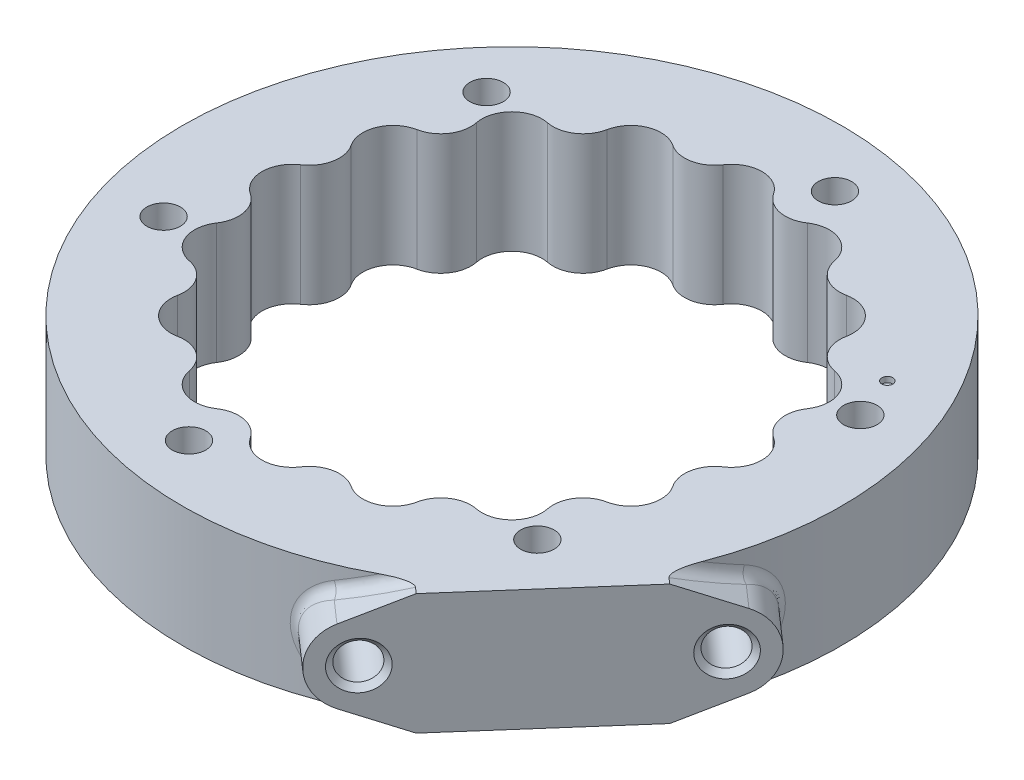
SolidWorks part; units mm, degrees
note: '?' marks a value the reader was unsure of.
ref_plane "Front Plane" through (0, 0, 0) normal (0, 0, 1) x (1, 0, 0)
ref_plane "Top Plane" through (0, 0, 0) normal (0, 1, 0) x (1, 0, 0)
ref_plane "Right Plane" through (0, 0, 0) normal (1, 0, 0) x (0, 0, -1)
sketch "Sketch1" plane through (0, 0, 0) normal (0, 1, 0) x (1, 0, 0)
  arc A0 (-31.5919, 24.5347) -> (-34.7568, 19.7981) centre (0, 0) ccw
  arc A1 (4.9902, 39.6875) -> (-4.9902, 39.6875) centre (0, 40) ccw
  arc A2 (19.7981, 34.7568) -> (10.5774, 38.5761) centre (15.3073, 36.9552) ccw
  arc A3 (-31.5919, 24.5347) -> (-34.7568, 19.7981) centre (0, 0) ccw construction
  arc A4 (31.5919, 24.5347) -> (24.5347, 31.5919) centre (28.2843, 28.2843) ccw
  arc A5 (-31.5919, 24.5347) -> (-34.7568, 19.7981) centre (0, 0) ccw construction
  arc A6 (38.5761, 10.5774) -> (34.7568, 19.7981) centre (36.9552, 15.3073) ccw
  arc A7 (-31.5919, 24.5347) -> (-34.7568, 19.7981) centre (0, 0) ccw construction
  arc A8 (39.6875, -4.9902) -> (39.6875, 4.9902) centre (40, 0) ccw
  arc A9 (-31.5919, 24.5347) -> (-34.7568, 19.7981) centre (0, 0) ccw construction
  arc A10 (34.7568, -19.7981) -> (38.5761, -10.5774) centre (36.9552, -15.3073) ccw
  arc A11 (-31.5919, 24.5347) -> (-34.7568, 19.7981) centre (0, 0) ccw construction
  arc A12 (24.5347, -31.5919) -> (31.5919, -24.5347) centre (28.2843, -28.2843) ccw
  arc A13 (-31.5919, 24.5347) -> (-34.7568, 19.7981) centre (0, 0) ccw construction
  arc A14 (10.5774, -38.5761) -> (19.7981, -34.7568) centre (15.3073, -36.9552) ccw
  arc A15 (-31.5919, 24.5347) -> (-34.7568, 19.7981) centre (0, 0) ccw construction
  arc A16 (-4.9902, -39.6875) -> (4.9902, -39.6875) centre (0, -40) ccw
  arc A17 (-31.5919, 24.5347) -> (-34.7568, 19.7981) centre (0, 0) ccw construction
  arc A18 (-19.7981, -34.7568) -> (-10.5774, -38.5761) centre (-15.3073, -36.9552) ccw
  arc A19 (-31.5919, 24.5347) -> (-34.7568, 19.7981) centre (0, 0) ccw construction
  arc A20 (-31.5919, -24.5347) -> (-24.5347, -31.5919) centre (-28.2843, -28.2843) ccw
  arc A21 (-31.5919, 24.5347) -> (-34.7568, 19.7981) centre (0, 0) ccw construction
  arc A22 (-38.5761, -10.5774) -> (-34.7568, -19.7981) centre (-36.9552, -15.3073) ccw
  arc A23 (-31.5919, 24.5347) -> (-34.7568, 19.7981) centre (0, 0) ccw construction
  arc A24 (-39.6875, 4.9902) -> (-39.6875, -4.9902) centre (-40, 0) ccw
  arc A25 (-31.5919, 24.5347) -> (-34.7568, 19.7981) centre (0, 0) ccw construction
  arc A26 (-34.7568, 19.7981) -> (-38.5761, 10.5774) centre (-36.9552, 15.3073) ccw
  arc A27 (-31.5919, 24.5347) -> (-34.7568, 19.7981) centre (0, 0) ccw construction
  arc A28 (-24.5347, 31.5919) -> (-31.5919, 24.5347) centre (-28.2843, 28.2843) ccw
  arc A29 (-31.5919, 24.5347) -> (-34.7568, 19.7981) centre (0, 0) ccw construction
  arc A30 (-10.5774, 38.5761) -> (-19.7981, 34.7568) centre (-15.3073, 36.9552) ccw
  arc A31 (-31.5919, 24.5347) -> (-34.7568, 19.7981) centre (0, 0) ccw construction
  circle A32 centre (0, 0) radius 60
  arc A33 (-19.7981, 34.7568) -> (-24.5347, 31.5919) centre (0, 0) ccw
  arc A34 (-19.7981, 34.7568) -> (-24.5347, 31.5919) centre (0, 0) ccw construction
  arc A35 (-19.7981, 34.7568) -> (-24.5347, 31.5919) centre (0, 0) ccw construction
  arc A36 (-19.7981, 34.7568) -> (-24.5347, 31.5919) centre (0, 0) ccw construction
  arc A37 (-19.7981, 34.7568) -> (-24.5347, 31.5919) centre (0, 0) ccw construction
  arc A38 (-19.7981, 34.7568) -> (-24.5347, 31.5919) centre (0, 0) ccw construction
  arc A39 (-19.7981, 34.7568) -> (-24.5347, 31.5919) centre (0, 0) ccw construction
  arc A40 (-19.7981, 34.7568) -> (-24.5347, 31.5919) centre (0, 0) ccw construction
  arc A41 (-19.7981, 34.7568) -> (-24.5347, 31.5919) centre (0, 0) ccw construction
  arc A42 (-19.7981, 34.7568) -> (-24.5347, 31.5919) centre (0, 0) ccw construction
  arc A43 (-19.7981, 34.7568) -> (-24.5347, 31.5919) centre (0, 0) ccw construction
  arc A44 (-19.7981, 34.7568) -> (-24.5347, 31.5919) centre (0, 0) ccw construction
  arc A45 (-19.7981, 34.7568) -> (-24.5347, 31.5919) centre (0, 0) ccw construction
  arc A46 (-19.7981, 34.7568) -> (-24.5347, 31.5919) centre (0, 0) ccw construction
  arc A47 (-19.7981, 34.7568) -> (-24.5347, 31.5919) centre (0, 0) ccw construction
  arc A48 (-19.7981, 34.7568) -> (-24.5347, 31.5919) centre (0, 0) ccw construction
  arc A49 (-4.9902, 39.6875) -> (-10.5774, 38.5761) centre (0, 0) ccw
  arc A50 (-4.9902, 39.6875) -> (-10.5774, 38.5761) centre (0, 0) ccw construction
  arc A51 (-4.9902, 39.6875) -> (-10.5774, 38.5761) centre (0, 0) ccw construction
  arc A52 (-4.9902, 39.6875) -> (-10.5774, 38.5761) centre (0, 0) ccw construction
  arc A53 (-4.9902, 39.6875) -> (-10.5774, 38.5761) centre (0, 0) ccw construction
  arc A54 (-4.9902, 39.6875) -> (-10.5774, 38.5761) centre (0, 0) ccw construction
  arc A55 (-4.9902, 39.6875) -> (-10.5774, 38.5761) centre (0, 0) ccw construction
  arc A56 (-4.9902, 39.6875) -> (-10.5774, 38.5761) centre (0, 0) ccw construction
  arc A57 (-4.9902, 39.6875) -> (-10.5774, 38.5761) centre (0, 0) ccw construction
  arc A58 (-4.9902, 39.6875) -> (-10.5774, 38.5761) centre (0, 0) ccw construction
  arc A59 (-4.9902, 39.6875) -> (-10.5774, 38.5761) centre (0, 0) ccw construction
  arc A60 (-4.9902, 39.6875) -> (-10.5774, 38.5761) centre (0, 0) ccw construction
  arc A61 (-4.9902, 39.6875) -> (-10.5774, 38.5761) centre (0, 0) ccw construction
  arc A62 (-4.9902, 39.6875) -> (-10.5774, 38.5761) centre (0, 0) ccw construction
  arc A63 (-4.9902, 39.6875) -> (-10.5774, 38.5761) centre (0, 0) ccw construction
  arc A64 (-4.9902, 39.6875) -> (-10.5774, 38.5761) centre (0, 0) ccw construction
  arc A65 (10.5774, 38.5761) -> (4.9902, 39.6875) centre (0, 0) ccw
  arc A66 (10.5774, 38.5761) -> (4.9902, 39.6875) centre (0, 0) ccw construction
  arc A67 (10.5774, 38.5761) -> (4.9902, 39.6875) centre (0, 0) ccw construction
  arc A68 (10.5774, 38.5761) -> (4.9902, 39.6875) centre (0, 0) ccw construction
  arc A69 (10.5774, 38.5761) -> (4.9902, 39.6875) centre (0, 0) ccw construction
  arc A70 (10.5774, 38.5761) -> (4.9902, 39.6875) centre (0, 0) ccw construction
  arc A71 (10.5774, 38.5761) -> (4.9902, 39.6875) centre (0, 0) ccw construction
  arc A72 (10.5774, 38.5761) -> (4.9902, 39.6875) centre (0, 0) ccw construction
  arc A73 (10.5774, 38.5761) -> (4.9902, 39.6875) centre (0, 0) ccw construction
  arc A74 (10.5774, 38.5761) -> (4.9902, 39.6875) centre (0, 0) ccw construction
  arc A75 (10.5774, 38.5761) -> (4.9902, 39.6875) centre (0, 0) ccw construction
  arc A76 (10.5774, 38.5761) -> (4.9902, 39.6875) centre (0, 0) ccw construction
  arc A77 (10.5774, 38.5761) -> (4.9902, 39.6875) centre (0, 0) ccw construction
  arc A78 (10.5774, 38.5761) -> (4.9902, 39.6875) centre (0, 0) ccw construction
  arc A79 (10.5774, 38.5761) -> (4.9902, 39.6875) centre (0, 0) ccw construction
  arc A80 (10.5774, 38.5761) -> (4.9902, 39.6875) centre (0, 0) ccw construction
  arc A81 (24.5347, 31.5919) -> (19.7981, 34.7568) centre (0, 0) ccw
  arc A82 (24.5347, 31.5919) -> (19.7981, 34.7568) centre (0, 0) ccw construction
  arc A83 (24.5347, 31.5919) -> (19.7981, 34.7568) centre (0, 0) ccw construction
  arc A84 (24.5347, 31.5919) -> (19.7981, 34.7568) centre (0, 0) ccw construction
  arc A85 (24.5347, 31.5919) -> (19.7981, 34.7568) centre (0, 0) ccw construction
  arc A86 (24.5347, 31.5919) -> (19.7981, 34.7568) centre (0, 0) ccw construction
  arc A87 (24.5347, 31.5919) -> (19.7981, 34.7568) centre (0, 0) ccw construction
  arc A88 (24.5347, 31.5919) -> (19.7981, 34.7568) centre (0, 0) ccw construction
  arc A89 (24.5347, 31.5919) -> (19.7981, 34.7568) centre (0, 0) ccw construction
  arc A90 (24.5347, 31.5919) -> (19.7981, 34.7568) centre (0, 0) ccw construction
  arc A91 (24.5347, 31.5919) -> (19.7981, 34.7568) centre (0, 0) ccw construction
  arc A92 (24.5347, 31.5919) -> (19.7981, 34.7568) centre (0, 0) ccw construction
  arc A93 (24.5347, 31.5919) -> (19.7981, 34.7568) centre (0, 0) ccw construction
  arc A94 (24.5347, 31.5919) -> (19.7981, 34.7568) centre (0, 0) ccw construction
  arc A95 (24.5347, 31.5919) -> (19.7981, 34.7568) centre (0, 0) ccw construction
  arc A96 (24.5347, 31.5919) -> (19.7981, 34.7568) centre (0, 0) ccw construction
  arc A97 (34.7568, 19.7981) -> (31.5919, 24.5347) centre (0, 0) ccw
  arc A98 (34.7568, 19.7981) -> (31.5919, 24.5347) centre (0, 0) ccw construction
  arc A99 (34.7568, 19.7981) -> (31.5919, 24.5347) centre (0, 0) ccw construction
  arc A100 (34.7568, 19.7981) -> (31.5919, 24.5347) centre (0, 0) ccw construction
  arc A101 (34.7568, 19.7981) -> (31.5919, 24.5347) centre (0, 0) ccw construction
  arc A102 (34.7568, 19.7981) -> (31.5919, 24.5347) centre (0, 0) ccw construction
  arc A103 (34.7568, 19.7981) -> (31.5919, 24.5347) centre (0, 0) ccw construction
  arc A104 (34.7568, 19.7981) -> (31.5919, 24.5347) centre (0, 0) ccw construction
  arc A105 (34.7568, 19.7981) -> (31.5919, 24.5347) centre (0, 0) ccw construction
  arc A106 (34.7568, 19.7981) -> (31.5919, 24.5347) centre (0, 0) ccw construction
  arc A107 (34.7568, 19.7981) -> (31.5919, 24.5347) centre (0, 0) ccw construction
  arc A108 (34.7568, 19.7981) -> (31.5919, 24.5347) centre (0, 0) ccw construction
  arc A109 (34.7568, 19.7981) -> (31.5919, 24.5347) centre (0, 0) ccw construction
  arc A110 (34.7568, 19.7981) -> (31.5919, 24.5347) centre (0, 0) ccw construction
  arc A111 (34.7568, 19.7981) -> (31.5919, 24.5347) centre (0, 0) ccw construction
  arc A112 (34.7568, 19.7981) -> (31.5919, 24.5347) centre (0, 0) ccw construction
  arc A113 (39.6875, 4.9902) -> (38.5761, 10.5774) centre (0, 0) ccw
  arc A114 (39.6875, 4.9902) -> (38.5761, 10.5774) centre (0, 0) ccw construction
  arc A115 (39.6875, 4.9902) -> (38.5761, 10.5774) centre (0, 0) ccw construction
  arc A116 (39.6875, 4.9902) -> (38.5761, 10.5774) centre (0, 0) ccw construction
  arc A117 (39.6875, 4.9902) -> (38.5761, 10.5774) centre (0, 0) ccw construction
  arc A118 (39.6875, 4.9902) -> (38.5761, 10.5774) centre (0, 0) ccw construction
  arc A119 (39.6875, 4.9902) -> (38.5761, 10.5774) centre (0, 0) ccw construction
  arc A120 (39.6875, 4.9902) -> (38.5761, 10.5774) centre (0, 0) ccw construction
  arc A121 (39.6875, 4.9902) -> (38.5761, 10.5774) centre (0, 0) ccw construction
  arc A122 (39.6875, 4.9902) -> (38.5761, 10.5774) centre (0, 0) ccw construction
  arc A123 (39.6875, 4.9902) -> (38.5761, 10.5774) centre (0, 0) ccw construction
  arc A124 (39.6875, 4.9902) -> (38.5761, 10.5774) centre (0, 0) ccw construction
  arc A125 (39.6875, 4.9902) -> (38.5761, 10.5774) centre (0, 0) ccw construction
  arc A126 (39.6875, 4.9902) -> (38.5761, 10.5774) centre (0, 0) ccw construction
  arc A127 (39.6875, 4.9902) -> (38.5761, 10.5774) centre (0, 0) ccw construction
  arc A128 (39.6875, 4.9902) -> (38.5761, 10.5774) centre (0, 0) ccw construction
  arc A129 (38.5761, -10.5774) -> (39.6875, -4.9902) centre (0, 0) ccw
  arc A130 (38.5761, -10.5774) -> (39.6875, -4.9902) centre (0, 0) ccw construction
  arc A131 (38.5761, -10.5774) -> (39.6875, -4.9902) centre (0, 0) ccw construction
  arc A132 (38.5761, -10.5774) -> (39.6875, -4.9902) centre (0, 0) ccw construction
  arc A133 (38.5761, -10.5774) -> (39.6875, -4.9902) centre (0, 0) ccw construction
  arc A134 (38.5761, -10.5774) -> (39.6875, -4.9902) centre (0, 0) ccw construction
  arc A135 (38.5761, -10.5774) -> (39.6875, -4.9902) centre (0, 0) ccw construction
  arc A136 (38.5761, -10.5774) -> (39.6875, -4.9902) centre (0, 0) ccw construction
  arc A137 (38.5761, -10.5774) -> (39.6875, -4.9902) centre (0, 0) ccw construction
  arc A138 (38.5761, -10.5774) -> (39.6875, -4.9902) centre (0, 0) ccw construction
  arc A139 (38.5761, -10.5774) -> (39.6875, -4.9902) centre (0, 0) ccw construction
  arc A140 (38.5761, -10.5774) -> (39.6875, -4.9902) centre (0, 0) ccw construction
  arc A141 (38.5761, -10.5774) -> (39.6875, -4.9902) centre (0, 0) ccw construction
  arc A142 (38.5761, -10.5774) -> (39.6875, -4.9902) centre (0, 0) ccw construction
  arc A143 (38.5761, -10.5774) -> (39.6875, -4.9902) centre (0, 0) ccw construction
  arc A144 (38.5761, -10.5774) -> (39.6875, -4.9902) centre (0, 0) ccw construction
  arc A145 (31.5919, -24.5347) -> (34.7568, -19.7981) centre (0, 0) ccw
  arc A146 (31.5919, -24.5347) -> (34.7568, -19.7981) centre (0, 0) ccw construction
  arc A147 (31.5919, -24.5347) -> (34.7568, -19.7981) centre (0, 0) ccw construction
  arc A148 (31.5919, -24.5347) -> (34.7568, -19.7981) centre (0, 0) ccw construction
  arc A149 (31.5919, -24.5347) -> (34.7568, -19.7981) centre (0, 0) ccw construction
  arc A150 (31.5919, -24.5347) -> (34.7568, -19.7981) centre (0, 0) ccw construction
  arc A151 (31.5919, -24.5347) -> (34.7568, -19.7981) centre (0, 0) ccw construction
  arc A152 (31.5919, -24.5347) -> (34.7568, -19.7981) centre (0, 0) ccw construction
  arc A153 (31.5919, -24.5347) -> (34.7568, -19.7981) centre (0, 0) ccw construction
  arc A154 (31.5919, -24.5347) -> (34.7568, -19.7981) centre (0, 0) ccw construction
  arc A155 (31.5919, -24.5347) -> (34.7568, -19.7981) centre (0, 0) ccw construction
  arc A156 (31.5919, -24.5347) -> (34.7568, -19.7981) centre (0, 0) ccw construction
  arc A157 (31.5919, -24.5347) -> (34.7568, -19.7981) centre (0, 0) ccw construction
  arc A158 (31.5919, -24.5347) -> (34.7568, -19.7981) centre (0, 0) ccw construction
  arc A159 (31.5919, -24.5347) -> (34.7568, -19.7981) centre (0, 0) ccw construction
  arc A160 (31.5919, -24.5347) -> (34.7568, -19.7981) centre (0, 0) ccw construction
  arc A161 (19.7981, -34.7568) -> (24.5347, -31.5919) centre (0, 0) ccw
  arc A162 (19.7981, -34.7568) -> (24.5347, -31.5919) centre (0, 0) ccw construction
  arc A163 (19.7981, -34.7568) -> (24.5347, -31.5919) centre (0, 0) ccw construction
  arc A164 (19.7981, -34.7568) -> (24.5347, -31.5919) centre (0, 0) ccw construction
  arc A165 (19.7981, -34.7568) -> (24.5347, -31.5919) centre (0, 0) ccw construction
  arc A166 (19.7981, -34.7568) -> (24.5347, -31.5919) centre (0, 0) ccw construction
  arc A167 (19.7981, -34.7568) -> (24.5347, -31.5919) centre (0, 0) ccw construction
  arc A168 (19.7981, -34.7568) -> (24.5347, -31.5919) centre (0, 0) ccw construction
  arc A169 (19.7981, -34.7568) -> (24.5347, -31.5919) centre (0, 0) ccw construction
  arc A170 (19.7981, -34.7568) -> (24.5347, -31.5919) centre (0, 0) ccw construction
  arc A171 (19.7981, -34.7568) -> (24.5347, -31.5919) centre (0, 0) ccw construction
  arc A172 (19.7981, -34.7568) -> (24.5347, -31.5919) centre (0, 0) ccw construction
  arc A173 (19.7981, -34.7568) -> (24.5347, -31.5919) centre (0, 0) ccw construction
  arc A174 (19.7981, -34.7568) -> (24.5347, -31.5919) centre (0, 0) ccw construction
  arc A175 (19.7981, -34.7568) -> (24.5347, -31.5919) centre (0, 0) ccw construction
  arc A176 (19.7981, -34.7568) -> (24.5347, -31.5919) centre (0, 0) ccw construction
  arc A177 (4.9902, -39.6875) -> (10.5774, -38.5761) centre (0, 0) ccw
  arc A178 (4.9902, -39.6875) -> (10.5774, -38.5761) centre (0, 0) ccw construction
  arc A179 (4.9902, -39.6875) -> (10.5774, -38.5761) centre (0, 0) ccw construction
  arc A180 (4.9902, -39.6875) -> (10.5774, -38.5761) centre (0, 0) ccw construction
  arc A181 (4.9902, -39.6875) -> (10.5774, -38.5761) centre (0, 0) ccw construction
  arc A182 (4.9902, -39.6875) -> (10.5774, -38.5761) centre (0, 0) ccw construction
  arc A183 (4.9902, -39.6875) -> (10.5774, -38.5761) centre (0, 0) ccw construction
  arc A184 (4.9902, -39.6875) -> (10.5774, -38.5761) centre (0, 0) ccw construction
  arc A185 (4.9902, -39.6875) -> (10.5774, -38.5761) centre (0, 0) ccw construction
  arc A186 (4.9902, -39.6875) -> (10.5774, -38.5761) centre (0, 0) ccw construction
  arc A187 (4.9902, -39.6875) -> (10.5774, -38.5761) centre (0, 0) ccw construction
  arc A188 (4.9902, -39.6875) -> (10.5774, -38.5761) centre (0, 0) ccw construction
  arc A189 (4.9902, -39.6875) -> (10.5774, -38.5761) centre (0, 0) ccw construction
  arc A190 (4.9902, -39.6875) -> (10.5774, -38.5761) centre (0, 0) ccw construction
  arc A191 (4.9902, -39.6875) -> (10.5774, -38.5761) centre (0, 0) ccw construction
  arc A192 (4.9902, -39.6875) -> (10.5774, -38.5761) centre (0, 0) ccw construction
  arc A193 (-10.5774, -38.5761) -> (-4.9902, -39.6875) centre (0, 0) ccw
  arc A194 (-10.5774, -38.5761) -> (-4.9902, -39.6875) centre (0, 0) ccw construction
  arc A195 (-10.5774, -38.5761) -> (-4.9902, -39.6875) centre (0, 0) ccw construction
  arc A196 (-10.5774, -38.5761) -> (-4.9902, -39.6875) centre (0, 0) ccw construction
  arc A197 (-10.5774, -38.5761) -> (-4.9902, -39.6875) centre (0, 0) ccw construction
  arc A198 (-10.5774, -38.5761) -> (-4.9902, -39.6875) centre (0, 0) ccw construction
  arc A199 (-10.5774, -38.5761) -> (-4.9902, -39.6875) centre (0, 0) ccw construction
  arc A200 (-10.5774, -38.5761) -> (-4.9902, -39.6875) centre (0, 0) ccw construction
  arc A201 (-10.5774, -38.5761) -> (-4.9902, -39.6875) centre (0, 0) ccw construction
  arc A202 (-10.5774, -38.5761) -> (-4.9902, -39.6875) centre (0, 0) ccw construction
  arc A203 (-10.5774, -38.5761) -> (-4.9902, -39.6875) centre (0, 0) ccw construction
  arc A204 (-10.5774, -38.5761) -> (-4.9902, -39.6875) centre (0, 0) ccw construction
  arc A205 (-10.5774, -38.5761) -> (-4.9902, -39.6875) centre (0, 0) ccw construction
  arc A206 (-10.5774, -38.5761) -> (-4.9902, -39.6875) centre (0, 0) ccw construction
  arc A207 (-10.5774, -38.5761) -> (-4.9902, -39.6875) centre (0, 0) ccw construction
  arc A208 (-10.5774, -38.5761) -> (-4.9902, -39.6875) centre (0, 0) ccw construction
  arc A209 (-24.5347, -31.5919) -> (-19.7981, -34.7568) centre (0, 0) ccw
  arc A210 (-24.5347, -31.5919) -> (-19.7981, -34.7568) centre (0, 0) ccw construction
  arc A211 (-24.5347, -31.5919) -> (-19.7981, -34.7568) centre (0, 0) ccw construction
  arc A212 (-24.5347, -31.5919) -> (-19.7981, -34.7568) centre (0, 0) ccw construction
  arc A213 (-24.5347, -31.5919) -> (-19.7981, -34.7568) centre (0, 0) ccw construction
  arc A214 (-24.5347, -31.5919) -> (-19.7981, -34.7568) centre (0, 0) ccw construction
  arc A215 (-24.5347, -31.5919) -> (-19.7981, -34.7568) centre (0, 0) ccw construction
  arc A216 (-24.5347, -31.5919) -> (-19.7981, -34.7568) centre (0, 0) ccw construction
  arc A217 (-24.5347, -31.5919) -> (-19.7981, -34.7568) centre (0, 0) ccw construction
  arc A218 (-24.5347, -31.5919) -> (-19.7981, -34.7568) centre (0, 0) ccw construction
  arc A219 (-24.5347, -31.5919) -> (-19.7981, -34.7568) centre (0, 0) ccw construction
  arc A220 (-24.5347, -31.5919) -> (-19.7981, -34.7568) centre (0, 0) ccw construction
  arc A221 (-24.5347, -31.5919) -> (-19.7981, -34.7568) centre (0, 0) ccw construction
  arc A222 (-24.5347, -31.5919) -> (-19.7981, -34.7568) centre (0, 0) ccw construction
  arc A223 (-24.5347, -31.5919) -> (-19.7981, -34.7568) centre (0, 0) ccw construction
  arc A224 (-24.5347, -31.5919) -> (-19.7981, -34.7568) centre (0, 0) ccw construction
  arc A225 (-34.7568, -19.7981) -> (-31.5919, -24.5347) centre (0, 0) ccw
  arc A226 (-34.7568, -19.7981) -> (-31.5919, -24.5347) centre (0, 0) ccw construction
  arc A227 (-34.7568, -19.7981) -> (-31.5919, -24.5347) centre (0, 0) ccw construction
  arc A228 (-34.7568, -19.7981) -> (-31.5919, -24.5347) centre (0, 0) ccw construction
  arc A229 (-34.7568, -19.7981) -> (-31.5919, -24.5347) centre (0, 0) ccw construction
  arc A230 (-34.7568, -19.7981) -> (-31.5919, -24.5347) centre (0, 0) ccw construction
  arc A231 (-34.7568, -19.7981) -> (-31.5919, -24.5347) centre (0, 0) ccw construction
  arc A232 (-34.7568, -19.7981) -> (-31.5919, -24.5347) centre (0, 0) ccw construction
  arc A233 (-34.7568, -19.7981) -> (-31.5919, -24.5347) centre (0, 0) ccw construction
  arc A234 (-34.7568, -19.7981) -> (-31.5919, -24.5347) centre (0, 0) ccw construction
  arc A235 (-34.7568, -19.7981) -> (-31.5919, -24.5347) centre (0, 0) ccw construction
  arc A236 (-34.7568, -19.7981) -> (-31.5919, -24.5347) centre (0, 0) ccw construction
  arc A237 (-34.7568, -19.7981) -> (-31.5919, -24.5347) centre (0, 0) ccw construction
  arc A238 (-34.7568, -19.7981) -> (-31.5919, -24.5347) centre (0, 0) ccw construction
  arc A239 (-34.7568, -19.7981) -> (-31.5919, -24.5347) centre (0, 0) ccw construction
  arc A240 (-34.7568, -19.7981) -> (-31.5919, -24.5347) centre (0, 0) ccw construction
  arc A241 (-39.6875, -4.9902) -> (-38.5761, -10.5774) centre (0, 0) ccw
  arc A242 (-39.6875, -4.9902) -> (-38.5761, -10.5774) centre (0, 0) ccw construction
  arc A243 (-39.6875, -4.9902) -> (-38.5761, -10.5774) centre (0, 0) ccw construction
  arc A244 (-39.6875, -4.9902) -> (-38.5761, -10.5774) centre (0, 0) ccw construction
  arc A245 (-39.6875, -4.9902) -> (-38.5761, -10.5774) centre (0, 0) ccw construction
  arc A246 (-39.6875, -4.9902) -> (-38.5761, -10.5774) centre (0, 0) ccw construction
  arc A247 (-39.6875, -4.9902) -> (-38.5761, -10.5774) centre (0, 0) ccw construction
  arc A248 (-39.6875, -4.9902) -> (-38.5761, -10.5774) centre (0, 0) ccw construction
  arc A249 (-39.6875, -4.9902) -> (-38.5761, -10.5774) centre (0, 0) ccw construction
  arc A250 (-39.6875, -4.9902) -> (-38.5761, -10.5774) centre (0, 0) ccw construction
  arc A251 (-39.6875, -4.9902) -> (-38.5761, -10.5774) centre (0, 0) ccw construction
  arc A252 (-39.6875, -4.9902) -> (-38.5761, -10.5774) centre (0, 0) ccw construction
  arc A253 (-39.6875, -4.9902) -> (-38.5761, -10.5774) centre (0, 0) ccw construction
  arc A254 (-39.6875, -4.9902) -> (-38.5761, -10.5774) centre (0, 0) ccw construction
  arc A255 (-39.6875, -4.9902) -> (-38.5761, -10.5774) centre (0, 0) ccw construction
  arc A256 (-39.6875, -4.9902) -> (-38.5761, -10.5774) centre (0, 0) ccw construction
  arc A257 (-38.5761, 10.5774) -> (-39.6875, 4.9902) centre (0, 0) ccw
  arc A258 (-38.5761, 10.5774) -> (-39.6875, 4.9902) centre (0, 0) ccw construction
  arc A259 (-38.5761, 10.5774) -> (-39.6875, 4.9902) centre (0, 0) ccw construction
  arc A260 (-38.5761, 10.5774) -> (-39.6875, 4.9902) centre (0, 0) ccw construction
  arc A261 (-38.5761, 10.5774) -> (-39.6875, 4.9902) centre (0, 0) ccw construction
  arc A262 (-38.5761, 10.5774) -> (-39.6875, 4.9902) centre (0, 0) ccw construction
  arc A263 (-38.5761, 10.5774) -> (-39.6875, 4.9902) centre (0, 0) ccw construction
  arc A264 (-38.5761, 10.5774) -> (-39.6875, 4.9902) centre (0, 0) ccw construction
  arc A265 (-38.5761, 10.5774) -> (-39.6875, 4.9902) centre (0, 0) ccw construction
  arc A266 (-38.5761, 10.5774) -> (-39.6875, 4.9902) centre (0, 0) ccw construction
  arc A267 (-38.5761, 10.5774) -> (-39.6875, 4.9902) centre (0, 0) ccw construction
  arc A268 (-38.5761, 10.5774) -> (-39.6875, 4.9902) centre (0, 0) ccw construction
  arc A269 (-38.5761, 10.5774) -> (-39.6875, 4.9902) centre (0, 0) ccw construction
  arc A270 (-38.5761, 10.5774) -> (-39.6875, 4.9902) centre (0, 0) ccw construction
  arc A271 (-38.5761, 10.5774) -> (-39.6875, 4.9902) centre (0, 0) ccw construction
  arc A272 (-38.5761, 10.5774) -> (-39.6875, 4.9902) centre (0, 0) ccw construction
  point P52 (0, 0)
  dimension "D1" = 80
  dimension "D2" = 10
  dimension "D4" = 120
  dimension "D3" = 16
extrude "Boss-Extrude1" add sketch "Sketch1" along normal blind 22
fillet "Fillet1" radius 5 32 edges at (-31.5919, 11, -24.5347) (-34.7568, 11, -19.7981) (10.5774, 11, 38.5761) (4.9902, 11, 39.6875) (-4.9902, 11, 39.6875) (-10.5774, 11, 38.5761) (-19.7981, 11, 34.7568) (-24.5347, 11, 31.5919) (-31.5919, 11, 24.5347) (-34.7568, 11, 19.7981) (-38.5761, 11, 10.5774) (-39.6875, 11, 4.9902) (-39.6875, 11, -4.9902) (-38.5761, 11, -10.5774) (19.7981, 11, 34.7568) (24.5347, 11, 31.5919) (31.5919, 11, 24.5347) (34.7568, 11, 19.7981) (38.5761, 11, 10.5774) (39.6875, 11, 4.9902) (39.6875, 11, -4.9902) (38.5761, 11, -10.5774) (34.7568, 11, -19.7981) (31.5919, 11, -24.5347) (24.5347, 11, -31.5919) (19.7981, 11, -34.7568) (10.5774, 11, -38.5761) (4.9902, 11, -39.6875) (-4.9902, 11, -39.6875) (-10.5774, 11, -38.5761) (-19.7981, 11, -34.7568) (-24.5347, 11, -31.5919)
fillet "Fillet2" radius 6 16 edges at (-7.8059, 11, 39.2431) (7.8059, 11, 39.2431) (22.2294, 11, 33.2687) (33.2687, 11, 22.2294) (-22.2294, 11, 33.2687) (-33.2687, 11, 22.2294) (-39.2431, 11, 7.8059) (-39.2431, 11, -7.8059) (39.2431, 11, 7.8059) (39.2431, 11, -7.8059) (33.2687, 11, -22.2294) (22.2294, 11, -33.2687) (7.8059, 11, -39.2431) (-7.8059, 11, -39.2431) (-22.2294, 11, -33.2687) (-33.2687, 11, -22.2294)
sketch "Sketch3" plane through (0, 22, 0) normal (0, 1, 0) x (1, 0, 0)
  line L0 (7.9956, 40.1966) -> (11.7054, 58.8471) construction
  circle A0 centre (0, 0) radius 50 construction
  circle A4 centre (9.7545, 49.0393) radius 3.05
  arc A5 (4.1664, 42.7642) -> (12.5159, 41.1034) centre (9.1661, 46.0813) ccw construction
  circle A6 centre (0, 0) radius 60 construction
  circle A7 centre (47.3465, 16.072) radius 3.05
  circle A8 centre (37.592, -32.9673) radius 3.05
  circle A9 centre (-9.7545, -49.0393) radius 3.05
  circle A10 centre (-47.3465, -16.072) radius 3.05
  circle A11 centre (-37.592, 32.9673) radius 3.05
  point P13 (9.1661, 46.0813)
  point P31 (0, 0)
  dimension "D1" = 100
  dimension "D2" = 6.1
  dimension "D3" = 6
extrude "Cut-Extrude1" cut sketch "Sketch3" against normal through all
ref_axis "Axis1" through (37.592, 0, 32.9673) along (0, 1, 0)?
ref_axis "Axis2" through (-9.7545, 0, 49.0393) along (0, 1, 0)?
ref_plane "Plane1" through (13.9187, 0, 41.0033) normal (-0.3214, 0, -0.9469) x (-0.9469, 0, 0.3214)
ref_plane "Plane2" through (19.2864, 0, 56.8158) normal (0.3214, 0, 0.9469) x (0.9469, 0, -0.3214)
ref_plane "Plane3" through (19.6078, 0, 57.7627) normal (0.3214, 0, 0.9469) x (0.9469, 0, -0.3214)
ref_plane "Plane4" through (45.1104, 0, 39.5607) normal (0.7518, 0, 0.6593) x (0, -1, 0)
ref_plane "Plane5" through (45.8622, 0, 40.2201) normal (0.7518, 0, 0.6593) x (0, -1, 0)
sketch "Sketch6" plane through (48.3229, 0, 37.4142) normal (-0.7518, 0, -0.6593) x (-0.6593, 0, 0.7518)
  line L0 (-56.2679, 0) -> (63.7321, 0) construction
  line L1 (-22.8416, 17.6775) -> (-2.6943, 26.1971)
  line L2 (10.1584, 26.1971) -> (30.3057, 17.6775)
  line L3 (-22.8416, 4.3225) -> (-2.6943, -4.1971)
  line L4 (10.1584, -4.1971) -> (30.3057, 4.3225)
  arc A0 (-2.6943, -4.1971) -> (10.1584, -4.1971) centre (3.7321, 11) ccw
  arc A1 (30.3057, 4.3225) -> (30.3057, 17.6775) centre (27.4821, 11) ccw
  arc A2 (-22.8416, 17.6775) -> (-22.8416, 4.3225) centre (-20.0179, 11) ccw
  arc A3 (10.1584, 26.1971) -> (-2.6943, 26.1971) centre (3.7321, 11) ccw
  dimension "D1" = 33
  dimension "D2" = 23.75
  dimension "D3" = 23.75
  dimension "D4" = 11
extrude "Boss-Extrude3" add sketch "Sketch6" against normal up to surface (1.3451 mm away)
sketch "Sketch7" plane through (45.8622, 0, 40.2201) normal (0.7518, 0, 0.6593) x (0.6593, 0, -0.7518)
  circle A0 centre (23.75, 11) radius 3.3
  circle A1 centre (-23.75, 11) radius 3.3
  dimension "D1" = 6.6
extrude "Cut-Extrude3" cut sketch "Sketch7" against normal blind 10.5
chamfer "Chamfer2" distance 1 angle 45 2 edges at (63.6975, 11, 19.8828) (32.3786, 11, 55.5952)
fillet "Fillet3" radius 2 6 edges at (56.3102, 19.8007, 20.7161) (56.3102, 2.1993, 20.7161) (27.8889, 2.1993, 53.1245) (27.8889, 19.8007, 53.1245) (59.03, 9.4978, 10.745) (18.3581, 12.5022, 57.1225)
sketch "Sketch8" plane through (45.8622, 0, 40.2201) normal (0.7518, 0, 0.6593) x (0.6593, 0, -0.7518)
  line L1 (-16.3518, 22) -> (16.3518, 22)
  line L2 (-16.3518, 22) -> (-16.3518, 27.5)
  line L3 (-16.3518, 27.5) -> (16.3518, 27.5)
  line L4 (16.3518, 22) -> (16.3518, 27.5)
  line L6 (-16.3518, -5.5) -> (16.3518, -5.5)
  line L7 (-16.3518, -5.5) -> (-16.3518, 0)
  line L8 (-16.3518, 0) -> (16.3518, 0)
  line L9 (16.3518, -5.5) -> (16.3518, 0)
  line L10 (26.5737, 4.3225) -> (6.4263, -4.1971) construction
  line L11 (60, 22) -> (-60, 22) construction
  arc A0 (6.4263, 26.1971) -> (-6.4263, 26.1971) centre (0, 11) ccw construction
  arc A1 (-6.4263, -4.1971) -> (6.4263, -4.1971) centre (0, 11) ccw construction
extrude "Cut-Extrude4" cut sketch "Sketch8" against normal through all
sketch "Sketch9" [suppressed] plane through (0, 22, 0) normal (0, 1, 0) x (1, 0, 0)
  circle A0 centre (44.4252, 23.9053) radius 1
  dimension "D1" = 2
extrude "Cut-Extrude5" [suppressed] cut sketch "Sketch9" against normal blind 1
sketch "Sketch10" plane through (0, 22, 0) normal (0, 1, 0) x (1, 0, 0)
  circle A0 centre (44.4252, 23.9053) radius 1
  dimension "D1" = 2
extrude "Cut-Extrude6" cut sketch "Sketch10" against normal blind 1
sketch "Sketch11" plane through (0, 22, 0) normal (0, 1, 0) x (1, 0, 0)
  arc A69 (-43.0406, 4.5831) -> (-43.0406, -4.5831) centre (-40, 0) ccw
  arc A70 (-43.0406, 4.5831) -> (-41.5182, 12.2367) centre (-46.0813, 9.1661) ccw
  arc A71 (-38.0105, 20.7051) -> (-41.5182, 12.2367) centre (-36.9552, 15.3073) ccw
  arc A72 (-38.0105, 20.7051) -> (-33.675, 27.1936) centre (-39.0658, 26.1029) ccw
  arc A73 (-27.1936, 33.675) -> (-33.675, 27.1936) centre (-28.2843, 28.2843) ccw
  arc A74 (-27.1936, 33.675) -> (-20.7051, 38.0105) centre (-26.1029, 39.0658) ccw
  arc A75 (-12.2367, 41.5182) -> (-20.7051, 38.0105) centre (-15.3073, 36.9552) ccw
  arc A76 (-41.5182, -12.2367) -> (-43.0406, -4.5831) centre (-46.0813, -9.1661) ccw
  arc A77 (-41.5182, -12.2367) -> (-38.0105, -20.7051) centre (-36.9552, -15.3073) ccw
  arc A78 (-33.675, -27.1936) -> (-38.0105, -20.7051) centre (-39.0658, -26.1029) ccw
  arc A79 (-33.675, -27.1936) -> (-27.1936, -33.675) centre (-28.2843, -28.2843) ccw
  arc A80 (-20.7051, -38.0105) -> (-27.1936, -33.675) centre (-26.1029, -39.0658) ccw
  arc A81 (-20.7051, -38.0105) -> (-12.2367, -41.5182) centre (-15.3073, -36.9552) ccw
  arc A82 (-4.5831, -43.0406) -> (-12.2367, -41.5182) centre (-9.1661, -46.0813) ccw
  arc A83 (-4.5831, -43.0406) -> (4.5831, -43.0406) centre (0, -40) ccw
  arc A84 (12.2367, -41.5182) -> (4.5831, -43.0406) centre (9.1661, -46.0813) ccw
  arc A85 (12.2367, -41.5182) -> (20.7051, -38.0105) centre (15.3073, -36.9552) ccw
  arc A86 (27.1936, -33.675) -> (20.7051, -38.0105) centre (26.1029, -39.0658) ccw
  arc A87 (27.1936, -33.675) -> (33.675, -27.1936) centre (28.2843, -28.2843) ccw
  arc A88 (38.0105, -20.7051) -> (33.675, -27.1936) centre (39.0658, -26.1029) ccw
  arc A89 (38.0105, -20.7051) -> (41.5182, -12.2367) centre (36.9552, -15.3073) ccw
  arc A90 (43.0406, -4.5831) -> (41.5182, -12.2367) centre (46.0813, -9.1661) ccw
  arc A91 (43.0406, -4.5831) -> (43.0406, 4.5831) centre (40, 0) ccw
  arc A92 (41.5182, 12.2367) -> (43.0406, 4.5831) centre (46.0813, 9.1661) ccw
  arc A93 (41.5182, 12.2367) -> (38.0105, 20.7051) centre (36.9552, 15.3073) ccw
  arc A94 (33.675, 27.1936) -> (38.0105, 20.7051) centre (39.0658, 26.1029) ccw
  arc A95 (33.675, 27.1936) -> (27.1936, 33.675) centre (28.2843, 28.2843) ccw
  arc A96 (20.7051, 38.0105) -> (27.1936, 33.675) centre (26.1029, 39.0658) ccw
  arc A97 (20.7051, 38.0105) -> (12.2367, 41.5182) centre (15.3073, 36.9552) ccw
  arc A98 (4.5831, 43.0406) -> (12.2367, 41.5182) centre (9.1661, 46.0813) ccw
  arc A99 (4.5831, 43.0406) -> (-4.5831, 43.0406) centre (0, 40) ccw
  arc A100 (-12.2367, 41.5182) -> (-4.5831, 43.0406) centre (-9.1661, 46.0813) ccw
  arc A101 (-43.0406, 4.5831) -> (-43.0406, -4.5831) centre (-40, 0) ccw
  arc A102 (-43.0406, 4.5831) -> (-41.5182, 12.2367) centre (-46.0813, 9.1661) ccw
  arc A103 (-38.0105, 20.7051) -> (-41.5182, 12.2367) centre (-36.9552, 15.3073) ccw
  arc A104 (-38.0105, 20.7051) -> (-33.675, 27.1936) centre (-39.0658, 26.1029) ccw
  arc A105 (-27.1936, 33.675) -> (-33.675, 27.1936) centre (-28.2843, 28.2843) ccw
  arc A106 (-27.1936, 33.675) -> (-20.7051, 38.0105) centre (-26.1029, 39.0658) ccw
  arc A107 (-12.2367, 41.5182) -> (-20.7051, 38.0105) centre (-15.3073, 36.9552) ccw
  arc A108 (-41.5182, -12.2367) -> (-43.0406, -4.5831) centre (-46.0813, -9.1661) ccw
  arc A109 (-41.5182, -12.2367) -> (-38.0105, -20.7051) centre (-36.9552, -15.3073) ccw
  arc A110 (-33.675, -27.1936) -> (-38.0105, -20.7051) centre (-39.0658, -26.1029) ccw
  arc A111 (-33.675, -27.1936) -> (-27.1936, -33.675) centre (-28.2843, -28.2843) ccw
  arc A112 (-20.7051, -38.0105) -> (-27.1936, -33.675) centre (-26.1029, -39.0658) ccw
  arc A113 (-20.7051, -38.0105) -> (-12.2367, -41.5182) centre (-15.3073, -36.9552) ccw
  arc A114 (-4.5831, -43.0406) -> (-12.2367, -41.5182) centre (-9.1661, -46.0813) ccw
  arc A115 (-4.5831, -43.0406) -> (4.5831, -43.0406) centre (0, -40) ccw
  arc A116 (12.2367, -41.5182) -> (4.5831, -43.0406) centre (9.1661, -46.0813) ccw
  arc A117 (12.2367, -41.5182) -> (20.7051, -38.0105) centre (15.3073, -36.9552) ccw
  arc A118 (27.1936, -33.675) -> (20.7051, -38.0105) centre (26.1029, -39.0658) ccw
  arc A119 (27.1936, -33.675) -> (33.675, -27.1936) centre (28.2843, -28.2843) ccw
  arc A120 (38.0105, -20.7051) -> (33.675, -27.1936) centre (39.0658, -26.1029) ccw
  arc A121 (38.0105, -20.7051) -> (41.5182, -12.2367) centre (36.9552, -15.3073) ccw
  arc A122 (43.0406, -4.5831) -> (41.5182, -12.2367) centre (46.0813, -9.1661) ccw
  arc A123 (43.0406, -4.5831) -> (43.0406, 4.5831) centre (40, 0) ccw
  arc A124 (41.5182, 12.2367) -> (43.0406, 4.5831) centre (46.0813, 9.1661) ccw
  arc A125 (41.5182, 12.2367) -> (38.0105, 20.7051) centre (36.9552, 15.3073) ccw
  arc A126 (33.675, 27.1936) -> (38.0105, 20.7051) centre (39.0658, 26.1029) ccw
  arc A127 (33.675, 27.1936) -> (27.1936, 33.675) centre (28.2843, 28.2843) ccw
  arc A128 (20.7051, 38.0105) -> (27.1936, 33.675) centre (26.1029, 39.0658) ccw
  arc A129 (20.7051, 38.0105) -> (12.2367, 41.5182) centre (15.3073, 36.9552) ccw
  arc A130 (4.5831, 43.0406) -> (12.2367, 41.5182) centre (9.1661, 46.0813) ccw
  arc A131 (4.5831, 43.0406) -> (-4.5831, 43.0406) centre (0, 40) ccw
  arc A132 (-12.2367, 41.5182) -> (-4.5831, 43.0406) centre (-9.1661, 46.0813) ccw
  dimension "D1" = 0.5
extrude "Cut-Extrude7" cut sketch "Sketch11" against normal through all
equation "\"R_ROLL\"= 5mm"
equation "\"D_SUN\"= 80mm"
equation "\"NUM_ROLL\"= 16"
equation "\"RHO\"= 1mm"
equation "\"D_SHAFT\"= 15mm"
equation "\"D_OUTPUT\"= 40mm"
equation "\"NUM_OUT\"= 6"
equation "\"R_OUT_ROLL\"= 5mm"
equation "\"D1@Sketch1\"=\"D_SUN\""
equation "\"D2@Sketch1\"=\"R_ROLL\"*2"
equation "\"D3@Sketch1\"=\"NUM_ROLL\""
equation "\"D4@Sketch1\"=\"D_SUN\"+40"
